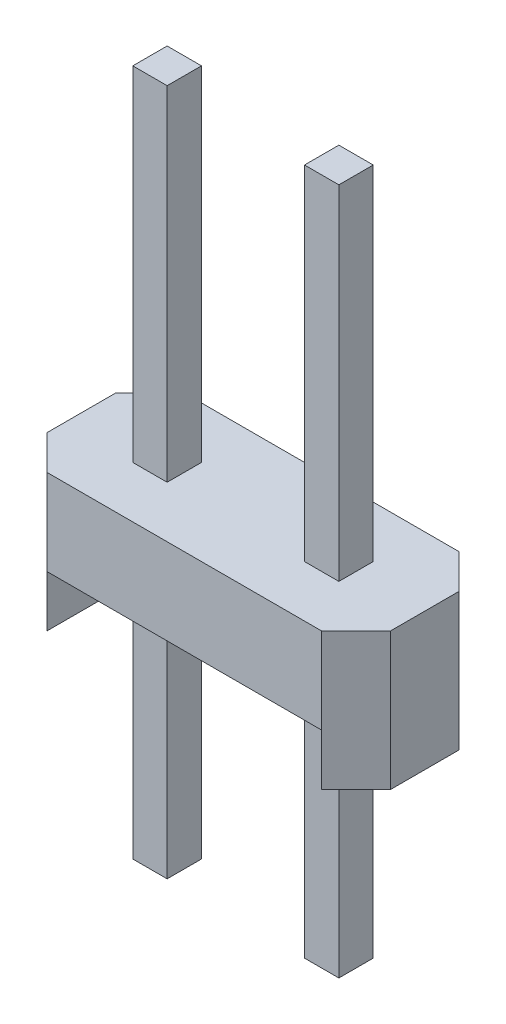
SolidWorks part; units mm, degrees
ref_plane "Front" through (0, 0, 0) normal (0, 0, 1) x (1, 0, 0)
ref_plane "Top" through (0, 0, 0) normal (0, 1, 0) x (1, 0, 0)
ref_plane "Right" through (0, 0, 0) normal (1, 0, 0) x (0, 0, -1)
sketch "Sketch1" plane through (0, 0, 0) normal (0, 1, 0) x (1, 0, 0)
  line L1 (0, 0) -> (5, 0)
  line L2 (0, 0) -> (0, 2)
  line L3 (0, 2) -> (5, 2)
  line L4 (5, 0) -> (5, 2)
  dimension "D1" = 5
  dimension "D2" = 2
extrude "Boss-Extrude1" add sketch "Sketch1" along normal blind 2
sketch "Sketch2" plane through (0, 0, 0) normal (0, 0, 1) x (1, 0, 0)
  line L0 (0, 0) -> (5, 0) construction
  line L1 (0.5, 0) -> (4.5, 0)
  line L2 (0.5, 0) -> (0.5, 0.75)
  line L3 (0.5, 0.75) -> (4.5, 0.75)
  line L4 (4.5, 0) -> (4.5, 0.75)
  line L5 (5, 2) -> (5, 0) construction
  dimension "D1" = 4
  dimension "D2" = 0.5
  dimension "D3" = 0.75
extrude "Cut-Extrude1" cut sketch "Sketch2" against normal through all
chamfer "Chamfer1" distance 0.5 angle 45 4 edges at (5, 1, 0) (5, 1, -2) (0, 1, -2) (0, 1, 0)
sketch "Sketch3" plane through (0, 2, 0) normal (0, 1, 0) x (1, 0, 0)
  line L0 (0, 1) -> (5, 1) construction
  line L1 (1, 1.25) -> (1.5, 1.25)
  line L2 (1, 1.25) -> (1, 0.75)
  line L3 (1, 0.75) -> (1.5, 0.75)
  line L4 (1.5, 1.25) -> (1.5, 0.75)
  line L5 (3.5, 1.25) -> (4, 1.25)
  line L6 (3.5, 1.25) -> (3.5, 0.75)
  line L7 (3.5, 0.75) -> (4, 0.75)
  line L8 (4, 1.25) -> (4, 0.75)
  line L11 (0, 1.5) -> (0, 0.5) construction
  line L12 (5, 0.5) -> (5, 1.5) construction
  line L13 (1, 1) -> (1.5, 1) construction
  line L14 (3.5, 1) -> (4, 1) construction
  dimension "D1" = 0.5
  dimension "D2" = 1
  dimension "D3" = 1
extrude "Boss-Extrude2" add sketch "Sketch3" along normal blind 5 and the other way blind 5
